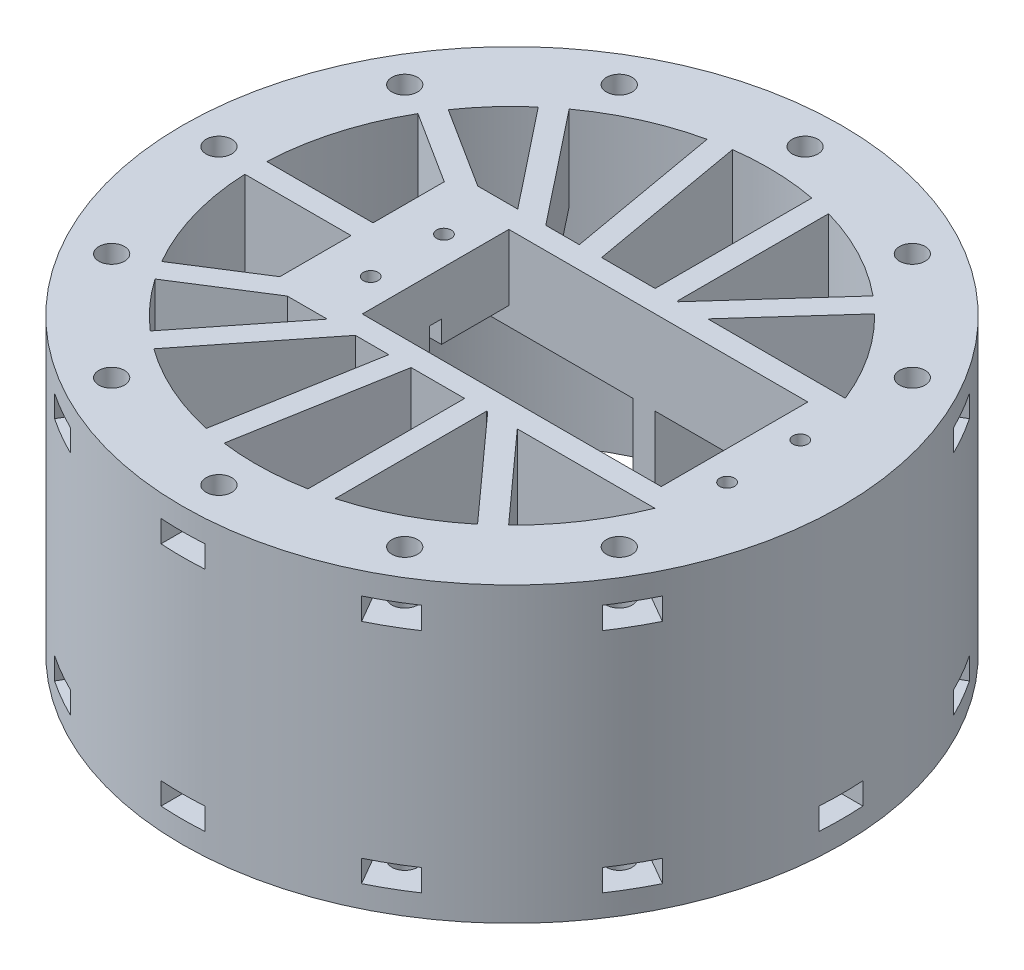
SolidWorks part; units mm, degrees
ref_plane "Front Plane" through (0, 0, 0) normal (0, 0, 1) x (1, 0, 0)
ref_plane "Top Plane" through (0, 0, 0) normal (0, 1, 0) x (1, 0, 0)
ref_plane "Right Plane" through (0, 0, 0) normal (1, 0, 0) x (0, 0, -1)
sketch "Sketch1" plane through (0, 0, 0) normal (0, 1, 0) x (1, 0, 0)
  line L0 (-43.0464, 0) -> (41.9462, 0) construction
  line L1 (0, 43.1152) -> (0, -41.8775) construction
  circle A1 centre (0, 0) radius 45
  dimension "D2" = 90
extrude "Boss-Extrude1" add sketch "Sketch1" along normal blind 40
sketch "Sketch2" plane through (0, 0, 0) normal (0, -1, 0) x (1, 0, 0)
  circle A0 centre (0, 0) radius 35
  dimension "D1" = 70
extrude "Cut-Extrude1" cut sketch "Sketch2" against normal blind 28.5
sketch "Sketch3" plane through (0, 28.5, 0) normal (0, -1, 0) x (1, 0, 0)
  line L0 (35, 0) -> (-35, 0) construction
  line L1 (0, -35) -> (0, 35) construction
  line L3 (37.5324, -10) -> (-17.4676, -10)
  line L4 (37.5324, -10) -> (37.5324, 10)
  line L5 (37.5324, 10) -> (-17.4676, 10)
  line L6 (-17.4676, -10) -> (-17.4676, 10)
  circle A0 centre (0, 0) radius 35 construction
  circle A1 centre (0, 0) radius 35 construction
  dimension "D1" = 20
  dimension "D2" = 55
  dimension "D3" = 10
  dimension "D4" = 37.5324
extrude "Cut-Extrude2" cut sketch "Sketch3" against normal blind 2.5 and the other way up to next
sketch "Sketch4" plane through (0, 31, 0) normal (0, -1, 0) x (1, 0, 0)
  line L0 (37.5324, 0) -> (-17.4676, 0) construction
  line L1 (37.5324, 10) -> (37.5324, -10) construction
  line L2 (-17.4676, 10) -> (-17.4676, -10) construction
  line L3 (0, -10) -> (0, 10) construction
  line L4 (-17.4676, -10) -> (33.541, -10) construction
  line L5 (33.541, 10) -> (-17.4676, 10) construction
  line L7 (30.3722, -10) -> (-10.4278, -10)
  line L8 (30.3722, -10) -> (30.3722, 10)
  line L9 (30.3722, 10) -> (-10.4278, 10)
  line L10 (-10.4278, -10) -> (-10.4278, 10)
  dimension "D1" = 20
  dimension "D2" = 40.8
  dimension "D3" = 30.3722
  dimension "D4" = 10
extrude "Cut-Extrude3" cut sketch "Sketch4" against normal blind 9
sketch "Sketch8" plane through (0, 28.5, 0) normal (0, -1, 0) x (1, 0, 0)
  line L0 (-17.4676, 0) -> (-35, 0) construction
  line L1 (-17.4676, 10) -> (-17.4676, -10) construction
  line L2 (8.0367, 10) -> (8.0367, 34.0648) construction
  line L3 (33.541, 10) -> (-17.4676, 10) construction
  line L4 (8.0367, -10) -> (8.0367, -29.3194) construction
  line L5 (-17.4676, -10) -> (33.541, -10) construction
  line L6 (6.5367, 10) -> (6.5367, 34.3842)
  line L7 (9.5367, 10) -> (9.5367, 33.6757)
  line L8 (9.5367, 10) -> (6.5367, 10)
  line L9 (9.5367, -10) -> (6.5367, -10)
  line L10 (6.5367, -10) -> (6.5367, -34.3842)
  line L11 (9.5367, -10) -> (9.5367, -33.6757)
  line L12 (-17.4676, 1.5) -> (-34.9678, 1.5)
  line L13 (-17.4676, -1.5) -> (-34.9678, -1.5)
  line L14 (-17.4676, 1.5) -> (-17.4676, -1.5)
  arc A0 (33.541, 10) -> (33.541, -10) centre (0, 0) ccw construction
  arc A1 (9.5367, 33.6757) -> (6.5367, 34.3842) centre (7.9531, 33.6757) ccw
  arc A2 (9.5367, -33.6757) -> (6.5367, -34.3842) centre (7.9531, -33.6757) cw
  arc A3 (-34.9678, 1.5) -> (-34.9678, -1.5) centre (-34.9678, 0) ccw
  dimension "D3" = 1.5
  dimension "D1" = 1.5
  dimension "D2" = 1.5
  dimension "D4" = 1.5
extrude "Boss-Extrude2" add sketch "Sketch8" along normal through all
sketch "Sketch16" plane through (0, 31, 0) normal (0, -1, 0) x (1, 0, 0)
  line L0 (-17.4676, 0) -> (37.5324, 0) construction
  line L1 (-17.4676, 10) -> (-17.4676, -10) construction
  line L2 (37.5324, -10) -> (37.5324, 10) construction
  line L3 (30.3722, -0.8) -> (37.5324, -0.8)
  line L4 (-10.4278, -0.8) -> (-17.4676, -0.8)
  line L5 (-10.4278, 10) -> (-10.4278, -10) construction
  line L6 (-10.4278, 0.8) -> (-17.4676, 0.8)
  line L7 (-17.4676, 0.8) -> (-17.4676, -0.8)
  line L8 (-10.4278, 0.8) -> (-10.4278, -0.8)
  line L9 (30.3722, -10) -> (30.3722, 10) construction
  line L10 (30.3722, 0.8) -> (37.5324, 0.8)
  line L11 (37.5324, 0.8) -> (37.5324, -0.8)
  line L12 (30.3722, 0.8) -> (30.3722, -0.8)
  dimension "D1" = 0.8
extrude "Cut-Extrude10" cut sketch "Sketch16" against normal blind 3
sketch "Sketch27" plane through (0, 0, 0) normal (0, -1, 0) x (1, 0, 0)
  line L0 (0, 0) -> (0, -53.17) construction
  line L1 (0, 0) -> (47.7582, -27.5732) construction
  line L3 (31.641, -18.2679) -> (31.641, -21.7321) construction
  line L4 (31.641, -21.7321) -> (34.641, -23.4641) construction
  line L5 (34.641, -23.4641) -> (37.641, -21.7321) construction
  line L6 (37.641, -21.7321) -> (37.641, -18.2679) construction
  line L7 (37.641, -18.2679) -> (34.641, -16.5359) construction
  line L8 (34.641, -16.5359) -> (31.641, -18.2679) construction
  circle A0 centre (0, 0) radius 40 construction
  circle A1 centre (34.641, -20) radius 1.75
  circle A2 centre (0, 0) radius 35 construction
  circle A3 centre (34.641, -20) radius 3 construction
  circle A4 centre (20, -34.641) radius 1.75
  circle A5 centre (0, -40) radius 1.75
  circle A6 centre (-20, -34.641) radius 1.75
  circle A7 centre (-34.641, -20) radius 1.75
  circle A8 centre (-40, 0) radius 1.75
  circle A9 centre (-34.641, 20) radius 1.75
  circle A10 centre (-20, 34.641) radius 1.75
  circle A11 centre (0, 40) radius 1.75
  circle A12 centre (20, 34.641) radius 1.75
  circle A13 centre (34.641, 20) radius 1.75
  circle A15 centre (40, 0) radius 1.75 [skipped]
  point P28 (0, 0)
  point P41 (0, 0)
  dimension "D1" = 80
  dimension "D3" = 3.5
  dimension "D4" = 70
  dimension "D5" = 6
  dimension "D6" = 12
  dimension "D2" = 60
extrude "Cut-Extrude15" cut sketch "Sketch27" against normal through all
ref_plane "Plane1" through (0, 37, 0) normal (0, 1, 0) x (1, 0, 0)
sketch "Sketch28" plane through (0, 37, 0) normal (0, 1, 0) x (1, 0, 0)
  line L0 (0, 0) -> (-54.493, 0) construction
  line L1 (-31.641, 18.2679) -> (-31.641, 21.7321)
  line L2 (-36.5359, 0) -> (-38.2679, 3)
  line L3 (-38.2679, 3) -> (-44.8999, 3)
  line L4 (-31.641, 21.7321) -> (-37.3844, 25.048)
  line L5 (-40.3844, 19.8519) -> (-34.641, 16.5359)
  line L6 (-44.8999, -3) -> (-38.2679, -3)
  line L7 (-38.2679, -3) -> (-36.5359, 0)
  line L8 (-43.4641, 0) -> (-42.5981, -1.5) [skipped]
  line L9 (-41.7321, 3) -> (-42.5981, 1.5) [skipped]
  line L10 (-34.641, 16.5359) -> (-31.641, 18.2679)
  line L11 (-18.2679, 31.641) -> (-16.5359, 34.641)
  line L12 (-16.5359, 34.641) -> (-19.8519, 40.3844)
  line L13 (-25.048, 37.3844) -> (-21.7321, 31.641)
  line L14 (-21.7321, 31.641) -> (-18.2679, 31.641)
  line L15 (0, 36.5359) -> (3, 38.2679)
  line L16 (3, 38.2679) -> (3, 44.8999)
  line L17 (-3, 44.8999) -> (-3, 38.2679)
  line L18 (-3, 38.2679) -> (0, 36.5359)
  line L19 (18.2679, 31.641) -> (21.7321, 31.641)
  line L20 (21.7321, 31.641) -> (25.048, 37.3844)
  line L21 (19.8519, 40.3844) -> (16.5359, 34.641)
  line L22 (16.5359, 34.641) -> (18.2679, 31.641)
  line L23 (31.641, 18.2679) -> (34.641, 16.5359)
  line L24 (34.641, 16.5359) -> (40.3844, 19.8519)
  line L25 (37.3844, 25.048) -> (31.641, 21.7321)
  line L26 (31.641, 21.7321) -> (31.641, 18.2679)
  line L31 (31.641, -18.2679) -> (31.641, -21.7321)
  line L32 (31.641, -21.7321) -> (37.3844, -25.048)
  line L33 (40.3844, -19.8519) -> (34.641, -16.5359)
  line L34 (34.641, -16.5359) -> (31.641, -18.2679)
  line L35 (18.2679, -31.641) -> (16.5359, -34.641)
  line L36 (16.5359, -34.641) -> (19.8519, -40.3844)
  line L37 (25.048, -37.3844) -> (21.7321, -31.641)
  line L38 (21.7321, -31.641) -> (18.2679, -31.641)
  line L39 (0, -36.5359) -> (-3, -38.2679)
  line L40 (-3, -38.2679) -> (-3, -44.8999)
  line L41 (3, -44.8999) -> (3, -38.2679)
  line L42 (3, -38.2679) -> (0, -36.5359)
  line L43 (-18.2679, -31.641) -> (-21.7321, -31.641)
  line L44 (-21.7321, -31.641) -> (-25.048, -37.3844)
  line L45 (-19.8519, -40.3844) -> (-16.5359, -34.641)
  line L46 (-16.5359, -34.641) -> (-18.2679, -31.641)
  line L47 (-31.641, -18.2679) -> (-34.641, -16.5359)
  line L48 (-34.641, -16.5359) -> (-40.3844, -19.8519)
  line L49 (-37.3844, -25.048) -> (-31.641, -21.7321)
  line L50 (-31.641, -21.7321) -> (-31.641, -18.2679)
  line L51 (36.5359, 0) -> (38.2679, -3) [skipped]
  line L52 (38.2679, -3) -> (44.8999, -3) [skipped]
  line L53 (44.8999, 3) -> (38.2679, 3) [skipped]
  line L54 (38.2679, 3) -> (36.5359, 0) [skipped]
  arc A0 (-44.8999, 3) -> (-44.8999, -3) centre (0, 0) ccw
  circle A1 centre (-40, 0) radius 3 construction
  arc A2 (-37.3844, 25.048) -> (-40.3844, 19.8519) centre (0, 0) ccw
  circle A3 centre (-34.641, 20) radius 3 construction
  arc A4 (-19.8519, 40.3844) -> (-25.048, 37.3844) centre (0, 0) ccw
  circle A5 centre (-20, 34.641) radius 3 construction
  arc A6 (3, 44.8999) -> (-3, 44.8999) centre (0, 0) ccw
  circle A7 centre (0, 40) radius 3 construction
  arc A8 (25.048, 37.3844) -> (19.8519, 40.3844) centre (0, 0) ccw
  circle A9 centre (20, 34.641) radius 3 construction
  arc A10 (40.3844, 19.8519) -> (37.3844, 25.048) centre (0, 0) ccw
  circle A11 centre (34.641, 20) radius 3 construction
  arc A14 (37.3844, -25.048) -> (40.3844, -19.8519) centre (0, 0) ccw
  circle A15 centre (34.641, -20) radius 3 construction
  arc A16 (19.8519, -40.3844) -> (25.048, -37.3844) centre (0, 0) ccw
  circle A17 centre (20, -34.641) radius 3 construction
  arc A18 (-3, -44.8999) -> (3, -44.8999) centre (0, 0) ccw
  circle A19 centre (0, -40) radius 3 construction
  arc A20 (-25.048, -37.3844) -> (-19.8519, -40.3844) centre (0, 0) ccw
  circle A21 centre (-20, -34.641) radius 3 construction
  arc A22 (-40.3844, -19.8519) -> (-37.3844, -25.048) centre (0, 0) ccw
  circle A23 centre (-34.641, -20) radius 3 construction
  arc A24 (44.8999, -3) -> (44.8999, 3) centre (0, 0) ccw [skipped]
  circle A25 centre (40, 0) radius 3 construction
  point P94 (0, 0)
  dimension "D1" = 90
  dimension "D2" = 6
  dimension "D3" = 12
extrude "Cut-Extrude17" cut sketch "Sketch28" against normal blind 3
sketch "Sketch29" plane through (0, 28.5, 0) normal (0, -1, 0) x (1, 0, 0)
  line L0 (32.4962, -13) -> (13.7255, -13)
  line L1 (9.5367, -33.6757) -> (9.5367, -10) construction
  line L2 (9.5367, -13) -> (9.5367, -33.6757)
  line L3 (9.5367, -10) -> (33.541, -10) construction
  line L4 (6.5367, -13) -> (-0.7691, -13)
  line L5 (6.5367, -10) -> (6.5367, -34.3842) construction
  line L6 (-20.4676, -11.223) -> (-20.4676, -1.5)
  line L7 (-34.9678, -1.5) -> (-17.4676, -1.5) construction
  line L8 (-20.4676, -1.5) -> (-34.9678, -1.5)
  line L9 (-17.4676, -0.8) -> (-17.4676, -10) construction
  line L10 (32.4962, 13) -> (13.7255, 13)
  line L11 (9.5367, 10) -> (9.5367, 33.6757) construction
  line L12 (9.5367, 13) -> (9.5367, 33.6757)
  line L13 (-7.5493, 34.1761) -> (-3.8154, 13)
  line L14 (6.5367, 13) -> (-0.7691, 13)
  line L15 (6.5367, 34.3842) -> (6.5367, 10) construction
  line L16 (-20.4676, 11.223) -> (-20.4676, 1.5)
  line L17 (-17.4676, 1.5) -> (-34.9678, 1.5) construction
  line L18 (-20.4676, 1.5) -> (-34.9678, 1.5)
  line L19 (6.5367, 13) -> (6.5367, 34.3842)
  line L20 (6.5367, -34.3842) -> (6.5367, -13)
  line L21 (0, 0) -> (-21.7353, -27.4331) construction
  line L22 (-20.5397, -28.3394) -> (-8.3862, -13)
  line L23 (-22.8911, -26.4764) -> (-12.2137, -13)
  line L24 (0, 0) -> (-20.4676, -13) construction
  line L25 (-17.6698, -13) -> (-28.713, -20.0141)
  line L26 (-20.4676, -11.223) -> (-30.3215, -17.4817)
  line L27 (0, 0) -> (-35, 0) construction
  line L28 (-20.4676, 11.223) -> (-30.3215, 17.4817)
  line L29 (-17.6698, 13) -> (-28.713, 20.0141)
  line L30 (-22.8911, 26.4764) -> (-12.2137, 13)
  line L31 (-20.5397, 28.3394) -> (-8.3862, 13)
  line L32 (-12.2137, 13) -> (-17.6698, 13)
  line L33 (0, 0) -> (-6.0777, -34.4683) construction
  line L34 (-4.5949, -34.6971) -> (-0.7691, -13)
  line L35 (-7.5493, -34.1761) -> (-3.8154, -13)
  line L36 (-3.8154, -13) -> (-17.6698, -13)
  line L37 (-4.5949, 34.6971) -> (-0.7691, 13)
  line L38 (-3.8154, 13) -> (-8.3862, 13)
  line L39 (0, 0) -> (23.4214, -26.0084) construction
  line L40 (9.6883, -13) -> (22.2852, -26.9883)
  line L41 (13.7255, -13) -> (24.5145, -24.9808)
  line L42 (13.7255, 13) -> (24.5145, 24.9808)
  line L43 (9.6883, 13) -> (22.2852, 26.9883)
  line L44 (9.6883, -13) -> (9.5367, -13)
  line L45 (9.6883, 13) -> (9.5367, 13)
  arc A0 (9.5367, -33.6757) -> (22.2852, -26.9883) centre (0, 0) ccw
  arc A1 (6.5367, 34.3842) -> (-4.5949, 34.6971) centre (0, 0) ccw
  arc A2 (32.4962, 13) -> (24.5145, 24.9808) centre (0, 0) ccw
  arc A3 (-34.9678, -1.5) -> (-30.3215, -17.4817) centre (0, 0) ccw
  circle A4 centre (0, 0) radius 35 construction
  arc A5 (-7.5493, 34.1761) -> (-20.5397, 28.3394) centre (0, 0) ccw
  arc A6 (-4.5949, -34.6971) -> (6.5367, -34.3842) centre (0, 0) ccw
  arc A7 (-20.5397, -28.3394) -> (-7.5493, -34.1761) centre (0, 0) ccw
  arc A8 (-28.713, -20.0141) -> (-22.8911, -26.4764) centre (0, 0) ccw
  arc A9 (-30.3215, 17.4817) -> (-34.9678, 1.5) centre (0, 0) ccw
  arc A10 (-22.8911, 26.4764) -> (-28.713, 20.0141) centre (0, 0) ccw
  arc A11 (24.5145, -24.9808) -> (32.4962, -13) centre (0, 0) ccw
  arc A12 (22.2852, 26.9883) -> (9.5367, 33.6757) centre (0, 0) ccw
  point P11 (21.5389, -10)
  point P23 (-17.4676, -5.4)
  line M3 (-17.4676, -1.5) -> (-34.9678, -1.5)
  arc M4 (-34.9678, -1.5) -> (6.5367, -34.3842) centre (0, 0) ccw
  line M5 (6.5367, -34.3842) -> (6.5367, -10)
  dimension "D1" = 1.5
  dimension "D2" = 3
  dimension "D3" = 3
  dimension "D4" = 80
  dimension "D5" = 1.5
  dimension "D6" = 1.5
  dimension "D7" = 1.5
sketch "Sketch32" plane through (0, 31, 0) normal (0, -1, 0) x (1, 0, 0)
  line L0 (-17.4676, 0) -> (37.5324, 0) construction
  line L1 (-17.4676, -1.5) -> (-17.4676, 1.5) construction
  line L2 (37.5324, 10) -> (37.5324, -10) construction
  line L3 (10.0324, 0) -> (10.0324, -10) construction
  line L6 (9.5367, -10) -> (33.541, -10) construction
  circle A0 centre (-14.2876, -5) radius 1
  circle A1 centre (-14.2876, 5) radius 1
  circle A2 centre (34.3524, -5) radius 1
  circle A3 centre (34.3524, 5) radius 1
  dimension "D1" = 24.32
  dimension "D3" = 2
  dimension "D2" = 5
extrude "Cut-Extrude21" cut sketch "Sketch32" against normal through all
extrude "Cut-Extrude22" cut sketch "Sketch29" against normal blind 12 contours L28 A9 L18 L16 | L26 L6 M3 M4 | L23 L36 L25 M4 | L35 L36 L22 M4 | L34 L4 M4 M5 | L2 A0 L40 L44 | L41 A11 L0 | L10 A2 L42 | L43 A12 L12 L45 | L19 A1 L37 L14 | L13 A5 L31 L38 | L30 A10 L29 L32 region at (23.89, 28.5, -17.1237) region at (13.9029, 28.5, -24.813) region at (1.8383, 28.5, -24.6789) region at (-27.5459, 28.5, -7.8919) region at (-10.8152, 28.5, -24.1049) region at (-20.9968, 28.5, -18.9781) region at (23.89, 28.5, 17.1237) region at (13.9029, 28.5, 24.813) region at (-10.8152, 28.5, 24.1049) region at (1.8383, 28.5, 24.6789) region at (-27.5459, 28.5, 7.8919) region at (-20.9968, 28.5, 18.9781)
sketch "Sketch33" plane through (0, 0, 1.5) normal (0, 0, 1) x (1, 0, 0)
  line L0 (-17.4676, 14.25) -> (-34.9678, 0)
  line L1 (-17.4676, 0) -> (-17.4676, 28.5) construction
  line L2 (-34.9678, 0) -> (-17.4676, 0)
  line L3 (-17.4676, 0) -> (-34.9678, 0) construction
  line L4 (-17.4676, 0) -> (-17.4676, 14.25)
extrude "Cut-Extrude23" cut sketch "Sketch33" against normal up to next
ref_plane "Plane2" through (0, 3, 0) normal (0, -1, 0) x (-1, 0, 0)
sketch "Sketch34" plane through (0, 3, 0) normal (0, -1, 0) x (-1, 0, 0)
  line L0 (0, 0) -> (0, 45) construction
  line L1 (18.2679, 31.641) -> (21.7321, 31.641)
  line L2 (0, 36.5359) -> (3, 38.2679)
  line L3 (3, 38.2679) -> (3, 44.8999)
  line L4 (21.7321, 31.641) -> (25.048, 37.3844)
  line L5 (19.8519, 40.3844) -> (16.5359, 34.641)
  line L6 (-3, 44.8999) -> (-3, 38.2679)
  line L7 (-3, 38.2679) -> (0, 36.5359)
  line L8 (0, 43.4641) -> (-1.5, 42.5981) [skipped]
  line L9 (3, 41.7321) -> (1.5, 42.5981) [skipped]
  line L10 (16.5359, 34.641) -> (18.2679, 31.641)
  line L11 (31.641, 18.2679) -> (34.641, 16.5359)
  line L12 (34.641, 16.5359) -> (40.3844, 19.8519)
  line L13 (37.3844, 25.048) -> (31.641, 21.7321)
  line L14 (31.641, 21.7321) -> (31.641, 18.2679)
  line L15 (36.5359, 0) -> (38.2679, -3)
  line L16 (38.2679, -3) -> (44.8999, -3)
  line L17 (44.8999, 3) -> (38.2679, 3)
  line L18 (38.2679, 3) -> (36.5359, 0)
  line L19 (31.641, -18.2679) -> (31.641, -21.7321)
  line L20 (31.641, -21.7321) -> (37.3844, -25.048)
  line L21 (40.3844, -19.8519) -> (34.641, -16.5359)
  line L22 (34.641, -16.5359) -> (31.641, -18.2679)
  line L23 (18.2679, -31.641) -> (16.5359, -34.641)
  line L24 (16.5359, -34.641) -> (19.8519, -40.3844)
  line L25 (25.048, -37.3844) -> (21.7321, -31.641)
  line L26 (21.7321, -31.641) -> (18.2679, -31.641)
  line L27 (0, -36.5359) -> (-3, -38.2679)
  line L28 (-3, -38.2679) -> (-3, -44.8999)
  line L29 (3, -44.8999) -> (3, -38.2679)
  line L30 (3, -38.2679) -> (0, -36.5359)
  line L31 (-18.2679, -31.641) -> (-21.7321, -31.641)
  line L32 (-21.7321, -31.641) -> (-25.048, -37.3844)
  line L33 (-19.8519, -40.3844) -> (-16.5359, -34.641)
  line L34 (-16.5359, -34.641) -> (-18.2679, -31.641)
  line L35 (-31.641, -18.2679) -> (-34.641, -16.5359)
  line L36 (-34.641, -16.5359) -> (-40.3844, -19.8519)
  line L37 (-37.3844, -25.048) -> (-31.641, -21.7321)
  line L38 (-31.641, -21.7321) -> (-31.641, -18.2679)
  line L39 (-36.5359, 0) -> (-38.2679, 3)
  line L40 (-38.2679, 3) -> (-44.8999, 3)
  line L41 (-44.8999, -3) -> (-38.2679, -3)
  line L42 (-38.2679, -3) -> (-36.5359, 0)
  line L43 (-31.641, 18.2679) -> (-31.641, 21.7321)
  line L44 (-31.641, 21.7321) -> (-37.3844, 25.048)
  line L45 (-40.3844, 19.8519) -> (-34.641, 16.5359)
  line L46 (-34.641, 16.5359) -> (-31.641, 18.2679)
  line L47 (-18.2679, 31.641) -> (-16.5359, 34.641)
  line L48 (-16.5359, 34.641) -> (-19.8519, 40.3844)
  line L49 (-25.048, 37.3844) -> (-21.7321, 31.641)
  line L50 (-21.7321, 31.641) -> (-18.2679, 31.641)
  circle A0 centre (0, 0) radius 45 construction
  circle A1 centre (0, 40) radius 3 construction
  arc A2 (3, 44.8999) -> (-3, 44.8999) centre (0, 0) ccw
  arc A3 (25.048, 37.3844) -> (19.8519, 40.3844) centre (0, 0) ccw
  circle A4 centre (20, 34.641) radius 3 construction
  arc A5 (40.3844, 19.8519) -> (37.3844, 25.048) centre (0, 0) ccw
  circle A6 centre (34.641, 20) radius 3 construction
  arc A7 (44.8999, -3) -> (44.8999, 3) centre (0, 0) ccw
  circle A8 centre (40, 0) radius 3 construction
  arc A9 (37.3844, -25.048) -> (40.3844, -19.8519) centre (0, 0) ccw
  circle A10 centre (34.641, -20) radius 3 construction
  arc A11 (19.8519, -40.3844) -> (25.048, -37.3844) centre (0, 0) ccw
  circle A12 centre (20, -34.641) radius 3 construction
  arc A13 (-3, -44.8999) -> (3, -44.8999) centre (0, 0) ccw
  circle A14 centre (0, -40) radius 3 construction
  arc A15 (-25.048, -37.3844) -> (-19.8519, -40.3844) centre (0, 0) ccw
  circle A16 centre (-20, -34.641) radius 3 construction
  arc A17 (-40.3844, -19.8519) -> (-37.3844, -25.048) centre (0, 0) ccw
  circle A18 centre (-34.641, -20) radius 3 construction
  arc A19 (-44.8999, 3) -> (-44.8999, -3) centre (0, 0) ccw
  circle A20 centre (-40, 0) radius 3 construction
  arc A21 (-37.3844, 25.048) -> (-40.3844, 19.8519) centre (0, 0) ccw
  circle A22 centre (-34.641, 20) radius 3 construction
  arc A23 (-19.8519, 40.3844) -> (-25.048, 37.3844) centre (0, 0) ccw
  circle A24 centre (-20, 34.641) radius 3 construction
  point P98 (0, 0)
  dimension "D1" = 6
  dimension "D2" = 90
  dimension "D3" = 12
extrude "Cut-Extrude24" cut sketch "Sketch34" against normal blind 3
